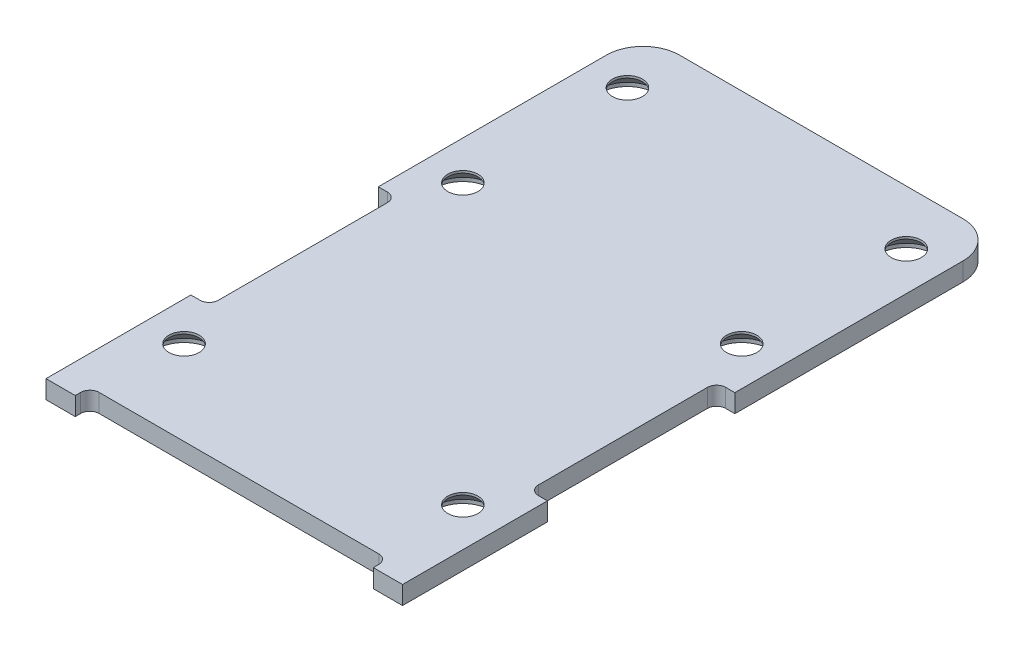
SolidWorks part; units mm, degrees
ref_plane "Front Plane" through (0, 0, 0) normal (0, 0, 1) x (1, 0, 0)
ref_plane "Top Plane" through (0, 0, 0) normal (0, 1, 0) x (1, 0, 0)
ref_plane "Right Plane" through (0, 0, 0) normal (1, 0, 0) x (0, 0, -1)
sketch "Sketch1" plane through (0, 0, 0) normal (0, 1, 0) x (1, 0, 0)
  line L1 (-18, 31.1) -> (18, 31.1)
  line L2 (-18, 31.1) -> (-18, -31.1)
  line L3 (-18, -31.1) -> (18, -31.1)
  line L4 (18, 31.1) -> (18, -31.1)
  line L5 (-18, 31.1) -> (18, -31.1) construction
  line L6 (-18, -31.1) -> (18, 31.1) construction
  point P0 (0, 0)
  dimension "D1" = 36
  dimension "D2" = 62.2
extrude "Base shape" add sketch "Sketch1" along normal blind 2
sketch "Sketch2" plane through (0, 2, 0) normal (0, 1, 0) x (1, 0, 0)
  line L0 (0, 31.1) -> (0, -31.1) construction
  line L1 (18, 31.1) -> (-18, 31.1) construction
  line L2 (-18, -31.1) -> (18, -31.1) construction
  line L4 (-18, 2.15) -> (-17.5, 2.15)
  line L5 (-18, 2.15) -> (-18, -18.35)
  line L6 (-18, -18.35) -> (-17.5, -18.35)
  line L7 (-17.5, 2.15) -> (-17.5, -18.35)
  line L8 (-17.5, -8.1) -> (-18, -8.1) construction
  line L9 (-15.25, -31.1) -> (-15.25, 31.1) construction
  line L11 (-18, -8.1) -> (18, -8.1) construction
  line L13 (15.25, 7.15) -> (15.25, -8.1) construction
  line L14 (15.25, 7.15) -> (0, 7.15) construction
  line L15 (18, -18.35) -> (17.5, -18.35)
  line L16 (17.5, 2.15) -> (17.5, -18.35)
  line L17 (18, 2.15) -> (17.5, 2.15)
  line L18 (18, 2.15) -> (18, -18.35)
  line L19 (18, -31.1) -> (18, 31.1) construction
  line L20 (-18, -31.1) -> (18, -31.1)
  line L21 (-18, -31.1) -> (-18, 14.9)
  line L22 (-18, 14.9) -> (18, 14.9)
  line L23 (18, -31.1) -> (18, 14.9)
  circle A0 centre (15.25, 7.15) radius 1.65
  circle A1 centre (15.25, -23.35) radius 1.65
  circle A2 centre (-15.25, 7.15) radius 1.65
  circle A3 centre (-15.25, -23.35) radius 1.65
  circle A4 centre (-15.25, 25.15) radius 1.65
  circle A5 centre (15.25, 25.15) radius 1.65
  line M13 (18, -31.1) -> (18, 31.1)
  line M15 (-18, 31.1) -> (-18, -31.1)
  dimension "D4" = 3.3
  dimension "D1" = 20.5
  dimension "D2" = 46
  dimension "D3" = 35
  dimension "D5" = 30.5
  dimension "D6" = 18
extrude "Cutouts" cut sketch "Sketch2" against normal up to next contours A2 | A0 | L17 L16 L15 M13 | L7 L4 L6 M15 | A3 | A1 | A4 | A5 region at (-17.75, 2, 8.1) region at (17.75, 2, 8.1) region at (15.25, 2, -7.15) region at (15.25, 2, 23.35) region at (-15.25, 2, -7.15) region at (-15.25, 2, 23.35)
sketch "Sketch3" plane through (0, 0, 0) normal (0, -1, 0) x (1, 0, 0)
  line L0 (18, -16.625) -> (19.5, -16.625) construction
  line L1 (19.5, 32.6) -> (-19.5, 32.6)
  line L2 (19.5, 32.6) -> (19.5, -32.6)
  line L3 (19.5, -32.6) -> (-19.5, -32.6)
  line L4 (-19.5, 32.6) -> (-19.5, -32.6)
  line L5 (19.5, 32.6) -> (-19.5, -32.6) construction
  line L6 (19.5, -32.6) -> (-19.5, 32.6) construction
  line L7 (0, -31.1) -> (0, -32.6) construction
  line L8 (-19.5, -31.1) -> (19.5, -31.1)
  line L9 (-19.5, -2.15) -> (19.5, -2.15)
  line L10 (-19.5, 18.35) -> (19.5, 18.35)
  line L11 (-19.5, 31.1) -> (19.5, 31.1)
  line L12 (-18, 18.35) -> (-17.5, 18.35)
  line L13 (-18, 31.1) -> (-18, 18.35)
  line L14 (18, 31.1) -> (-18, 31.1)
  line L15 (18, 18.35) -> (18, 31.1)
  line L16 (17.5, 18.35) -> (18, 18.35)
  line L17 (17.5, -2.15) -> (17.5, 18.35)
  line L18 (18, -2.15) -> (17.5, -2.15)
  line L19 (18, -31.1) -> (18, -2.15)
  line L20 (-18, -31.1) -> (18, -31.1)
  line L21 (-18, -2.15) -> (-18, -31.1)
  line L22 (-17.5, -2.15) -> (-18, -2.15)
  line L23 (-17.5, 18.35) -> (-17.5, -2.15)
  line L24 (-18, 18.35) -> (-17.5, 18.35)
  line L25 (-18, 31.1) -> (-18, 18.35)
  line L26 (18, 31.1) -> (-18, 31.1)
  line L27 (18, 18.35) -> (18, 31.1)
  line L28 (17.5, 18.35) -> (18, 18.35)
  line L29 (17.5, -2.15) -> (17.5, 18.35)
  line L30 (18, -2.15) -> (17.5, -2.15)
  line L31 (18, -31.1) -> (18, -2.15)
  line L32 (-18, -31.1) -> (18, -31.1)
  line L33 (-18, -2.15) -> (-18, -31.1)
  line L34 (-17.5, -2.15) -> (-18, -2.15)
  line L35 (-17.5, 18.35) -> (-17.5, -2.15)
  point P2 (0, 0)
  line M15 (18, -31.1) -> (18, -2.15)
  line M16 (18, 31.1) -> (-18, 31.1)
  line M17 (-18, 31.1) -> (-18, 18.35)
  line M35 (-18, -2.15) -> (-18, -31.1)
  line M36 (18, 18.35) -> (18, 31.1)
  dimension "D2" = 1.5
  dimension "D1" = 0
extrude "Extra size" add sketch "Sketch3" against normal up to surface (2 mm away) contours L9 L4 L8 M35 | L9 L8 L2 M15 | L11 L4 L10 M17 | L11 L10 L2 M36 | L4 L11 L2 L1 M16 region at (0, 0, 31.85) region at (18.75, 0, 24.725) region at (-18.75, 0, 24.725) region at (18.75, 0, -16.625) region at (-18.75, 0, -16.625) up to face at (15.25, 2, 25)
sketch "Sketch4" plane through (0, 0, 0) normal (0, 1, 0) x (1, 0, 0)
  circle A0 centre (-15.25, 25.15) radius 3
  circle A1 centre (15.25, 25.15) radius 3
  circle A2 centre (15.25, 7.15) radius 3
  circle A3 centre (-15.25, 7.15) radius 3
  circle A4 centre (-15.25, -23.35) radius 3
  circle A5 centre (15.25, -23.35) radius 3
  dimension "D1" = 6
extrude "Screw head cut" cut sketch "Sketch4" along normal blind 0.4
chamfer "Screw chamfer" distance 1.35 angle 45 6 edges at (-15.25, 0.4, 25) (15.25, 0.4, 25) (15.25, 0.4, -5.5) (15.25, 0.4, -23.5) (-15.25, 0.4, -23.5) (-15.25, 0.4, -5.5)
fillet "Front fillets" radius 4 2 edges at (19.5, 1, -31.1) (-19.5, 1, -31.1)
sketch "Sketch6" plane through (0, 0, 32.6) normal (0, 0, 1) x (1, 0, 0)
  line L0 (19.5, 0) -> (-19.5, 0) construction
  line L1 (19.5, 2) -> (16.3, 2)
  line L2 (19.5, 2) -> (19.5, 0)
  line L3 (19.5, 0) -> (16.3, 0)
  line L4 (16.3, 2) -> (16.3, 0)
  line L5 (16.3, 10.2) -> (16.3, 2) construction
  line L6 (-16.3, 2) -> (-16.3, 10.2) construction
  line L7 (-19.5, 0) -> (-16.3, 0)
  line L8 (-19.5, 0) -> (-19.5, 2)
  line L9 (-19.5, 2) -> (-16.3, 2)
  line L10 (-16.3, 0) -> (-16.3, 2)
  line L11 (19.5, 2) -> (-19.5, 2) construction
extrude "Ledbar sides" add sketch "Sketch6" along normal up to surface (1.6 mm away)
fillet "Milling fillets" radius 1 6 edges at (-16.3, 1, 32.6) (16.3, 1, 32.6) (17.5, 1, -2.15) (17.5, 1, 18.35) (-17.5, 1, -2.15) (-17.5, 1, 18.35)
